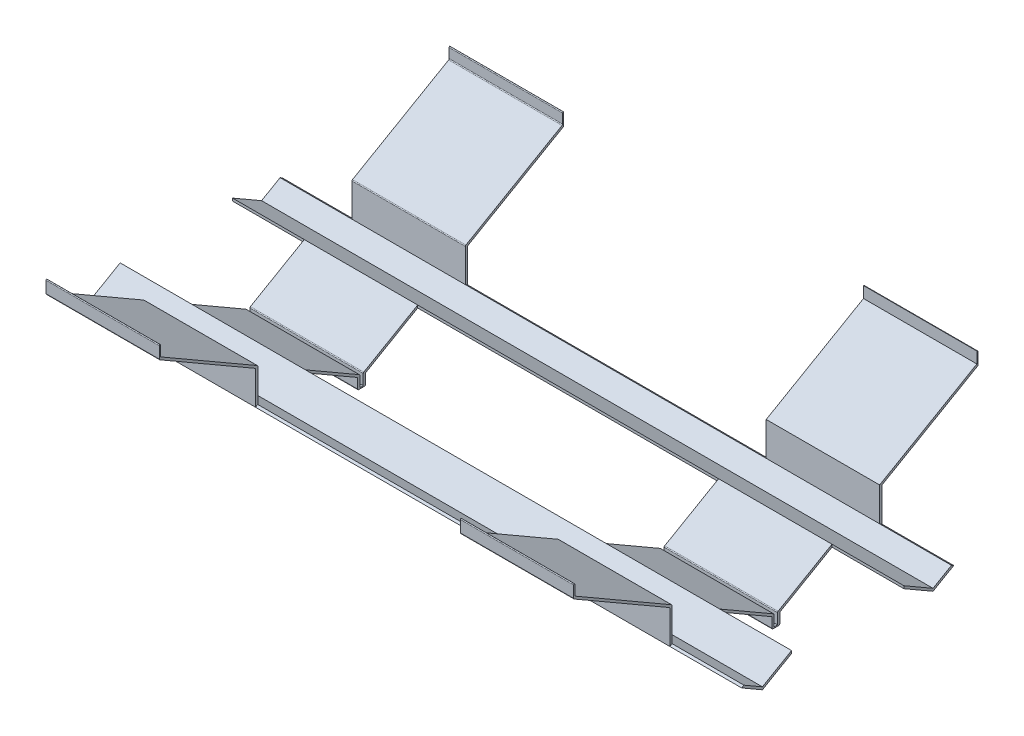
SolidWorks part; units mm, degrees
ref_plane "Front Plane" through (0, 0, 0) normal (0, 0, 1) x (1, 0, 0)
ref_plane "Top Plane" through (0, 0, 0) normal (0, 1, 0) x (1, 0, 0)
ref_plane "Right Plane" through (0, 0, 0) normal (1, 0, 0) x (0, 0, -1)
sketch "Sketch1" plane through (0, 0, 0) normal (1, 0, 0) x (0, 0, -1)
  line L1 (-7.5, 5) -> (7.5, 5)
  line L2 (7.5, 5) -> (7.5, 55)
  line L3 (7.5, 55) -> (249.9871, 195)
  line L4 (249.9871, 195) -> (379.8909, 120)
  line L5 (379.8909, 120) -> (462.1633, 167.5)
  line L6 (462.1633, 167.5) -> (462.1633, 317.5)
  line L7 (462.1633, 317.5) -> (895.176, 567.5)
  line L8 (895.176, 567.5) -> (895.176, 617.5)
  line L9 (895.176, 617.5) -> (900.176, 617.5)
  line L10 (900.176, 617.5) -> (900.176, 558.8397)
  line L11 (900.176, 558.8397) -> (472.1633, 311.7265)
  line L12 (472.1633, 311.7265) -> (472.1633, 161.7265)
  line L13 (472.1633, 161.7265) -> (379.8909, 108.453)
  line L14 (379.8909, 108.453) -> (249.9871, 183.453)
  line L15 (249.9871, 183.453) -> (17.5, 49.2265)
  line L16 (17.5, 49.2265) -> (17.5, 0)
  line L17 (17.5, 0) -> (-17.5, 0)
  line L18 (0, -6.3719) -> (0, 0) construction
  line L19 (-17.5, 49.2265) -> (-17.5, 0)
  line L20 (-249.9871, 183.453) -> (-17.5, 49.2265)
  line L21 (-379.8909, 108.453) -> (-249.9871, 183.453)
  line L22 (-472.1633, 161.7265) -> (-379.8909, 108.453)
  line L23 (-472.1633, 311.7265) -> (-472.1633, 161.7265)
  line L24 (-900.176, 558.8397) -> (-472.1633, 311.7265)
  line L25 (-900.176, 617.5) -> (-900.176, 558.8397)
  line L26 (-895.176, 617.5) -> (-900.176, 617.5)
  line L27 (-895.176, 567.5) -> (-895.176, 617.5)
  line L28 (-462.1633, 317.5) -> (-895.176, 567.5)
  line L29 (-462.1633, 167.5) -> (-462.1633, 317.5)
  line L30 (-379.8909, 120) -> (-462.1633, 167.5)
  line L31 (-249.9871, 195) -> (-379.8909, 120)
  line L32 (-7.5, 55) -> (-249.9871, 195)
  line L33 (-7.5, 5) -> (-7.5, 55)
  line L34 (0, 5) -> (0, 23.7609) construction
  dimension "D2" = 10
  dimension "D3" = 10
  dimension "D4" = 120
  dimension "D5" = 10
  dimension "D6" = 120
  dimension "D7" = 120
  dimension "D8" = 10
  dimension "D9" = 10
  dimension "D10" = 10
  dimension "D11" = 280
  dimension "D12" = 500
  dimension "D13" = 5
  dimension "D14" = 5
  dimension "D15" = 120
  dimension "D16" = 245
  dimension "D17" = 150
  dimension "D18" = 7.5
  dimension "D19" = 50
  dimension "D20" = 50
extrude "Boss-Extrude1" add sketch "Sketch1" along normal blind 505
sketch "Sketch2" plane through (505, 0, 0) normal (1, 0, 0) x (0, 0, -1)
  line L0 (249.9871, 195) -> (379.8909, 120)
  line L1 (379.8909, 120) -> (462.1633, 167.5)
  line L2 (462.1633, 167.5) -> (472.1633, 161.7265)
  line L3 (472.1633, 161.7265) -> (379.8909, 108.453)
  line L4 (379.8909, 108.453) -> (249.9871, 183.453)
  line L5 (249.9871, 183.453) -> (249.9871, 195)
  line L6 (-462.1633, 167.5) -> (-379.8909, 120)
  line L7 (-379.8909, 120) -> (-249.9871, 195)
  line L8 (-249.9871, 195) -> (-249.9871, 183.453)
  line L9 (-249.9871, 183.453) -> (-379.8909, 108.453)
  line L10 (-379.8909, 108.453) -> (-472.1633, 161.7265)
  line L11 (-472.1633, 161.7265) -> (-462.1633, 167.5)
extrude "Boss-Extrude3" add sketch "Sketch2" along normal blind 1340 and the other way blind 825
sketch "Sketch4" plane through (1845, 0, 0) normal (1, 0, 0) x (0, 0, -1)
  line L0 (-900.176, 617.5) -> (-895.176, 617.5)
  line L1 (-895.176, 617.5) -> (-895.176, 567.5)
  line L2 (-895.176, 567.5) -> (-462.1633, 317.5)
  line L3 (-462.1633, 317.5) -> (-462.1633, 167.5)
  line L4 (-462.1633, 167.5) -> (-379.8909, 120)
  line L5 (-379.8909, 120) -> (-249.9871, 195)
  line L6 (-249.9871, 195) -> (-7.5, 55)
  line L7 (-7.5, 55) -> (-7.5, 5)
  line L8 (-7.5, 5) -> (7.5, 5)
  line L9 (7.5, 5) -> (7.5, 55)
  line L10 (7.5, 55) -> (249.9871, 195)
  line L11 (249.9871, 195) -> (379.8909, 120)
  line L12 (379.8909, 120) -> (462.1633, 167.5)
  line L13 (462.1633, 167.5) -> (462.1633, 317.5)
  line L14 (462.1633, 317.5) -> (895.176, 567.5)
  line L15 (895.176, 567.5) -> (895.176, 617.5)
  line L16 (895.176, 617.5) -> (900.176, 617.5)
  line L17 (900.176, 617.5) -> (900.176, 558.8397)
  line L18 (900.176, 558.8397) -> (472.1633, 311.7265)
  line L19 (472.1633, 311.7265) -> (472.1633, 161.7265)
  line L20 (472.1633, 161.7265) -> (379.8909, 108.453)
  line L21 (379.8909, 108.453) -> (249.9871, 183.453)
  line L22 (249.9871, 183.453) -> (17.5, 49.2265)
  line L23 (17.5, 49.2265) -> (17.5, 0)
  line L24 (17.5, 0) -> (-17.5, 0)
  line L25 (-17.5, 0) -> (-17.5, 49.2265)
  line L26 (-17.5, 49.2265) -> (-249.9871, 183.453)
  line L27 (-249.9871, 183.453) -> (-379.8909, 108.453)
  line L28 (-379.8909, 108.453) -> (-472.1633, 161.7265)
  line L29 (-472.1633, 161.7265) -> (-472.1633, 311.7265)
  line L30 (-472.1633, 311.7265) -> (-900.176, 558.8397)
  line L31 (-900.176, 558.8397) -> (-900.176, 617.5)
extrude "Boss-Extrude4" add sketch "Sketch4" along normal blind 505
sketch "Sketch5" plane through (2350, 0, 0) normal (1, 0, 0) x (0, 0, -1)
  line L0 (249.9871, 195) -> (379.8909, 120)
  line L1 (379.8909, 120) -> (462.1633, 167.5)
  line L2 (462.1633, 167.5) -> (472.1633, 161.7265)
  line L3 (472.1633, 161.7265) -> (379.8909, 108.453)
  line L4 (379.8909, 108.453) -> (249.9871, 183.453)
  line L5 (249.9871, 183.453) -> (249.9871, 195)
  line L6 (-462.1633, 167.5) -> (-379.8909, 120)
  line L7 (-379.8909, 120) -> (-249.9871, 195)
  line L8 (-249.9871, 195) -> (-249.9871, 183.453)
  line L9 (-249.9871, 183.453) -> (-379.8909, 108.453)
  line L10 (-379.8909, 108.453) -> (-472.1633, 161.7265)
  line L11 (-472.1633, 161.7265) -> (-462.1633, 167.5)
extrude "Boss-Extrude5" add sketch "Sketch5" along normal blind 320
fillet "Fillet1" radius 5 29 edges at (252.5, 617.5, -895.176) (252.5, 567.5, -895.176) (252.5, 317.5, -462.1633) (252.5, 311.7265, -472.1633) (252.5, 558.8397, -900.176) (252.5, 617.5, -900.176) (2097.5, 617.5, -900.176) (2097.5, 558.8397, -900.176) (2097.5, 311.7265, -472.1633) (252.5, 311.7265, 472.1633) (2097.5, 311.7265, 472.1633) (2097.5, 317.5, 462.1633) (252.5, 317.5, 462.1633) (252.5, 567.5, 895.176) (252.5, 617.5, 895.176) (252.5, 617.5, 900.176) (252.5, 558.8397, 900.176) (2097.5, 558.8397, 900.176) (2097.5, 567.5, 895.176) (2097.5, 617.5, 895.176) (2097.5, 617.5, 900.176) (252.5, 0, 17.5) (252.5, 0, -17.5) (252.5, 55, -7.5) (252.5, 55, 7.5) (2097.5, 0, -17.5) (2097.5, 0, 17.5) (2097.5, 55, -7.5) (2097.5, 55, 7.5)
